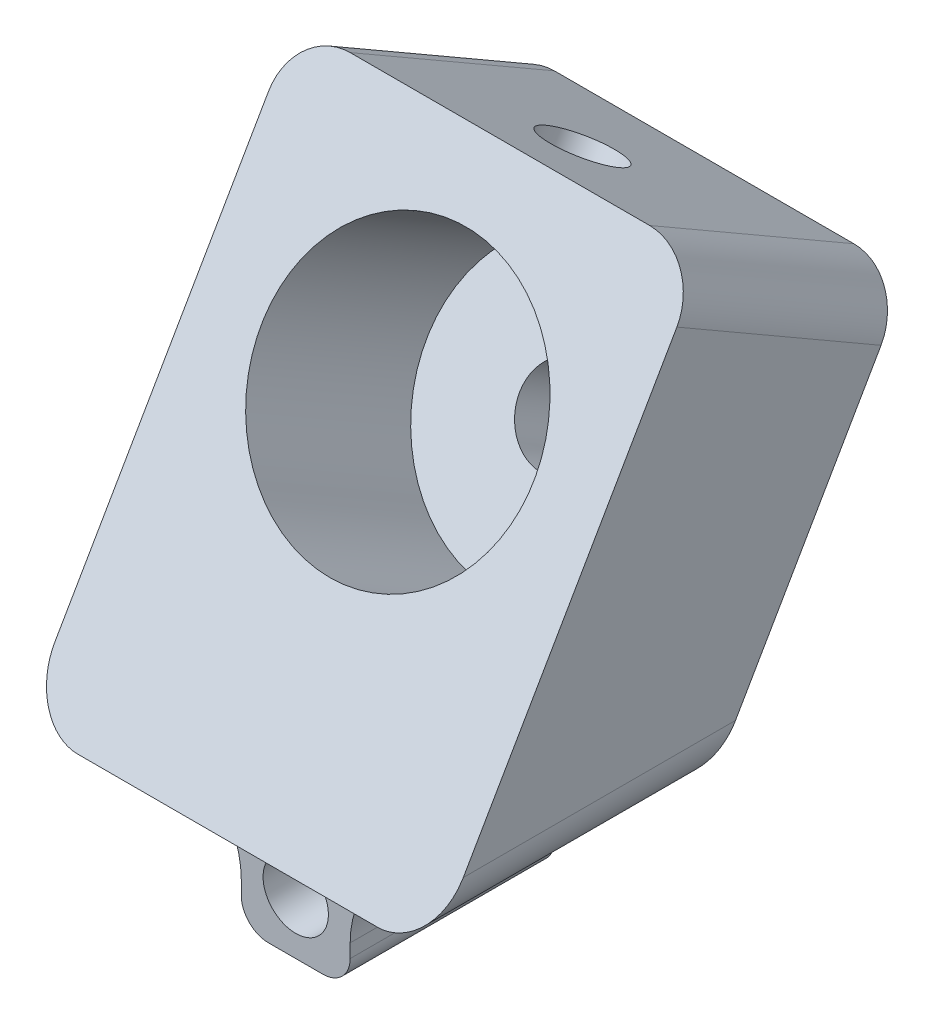
SolidWorks part; units mm, degrees
note: '?' marks a value the reader was unsure of.
ref_plane "Front Plane" through (0, 0, 0) normal (0, 0, 1) x (1, 0, 0)
ref_plane "Top Plane" through (0, 0, 0) normal (0, 1, 0) x (1, 0, 0)
ref_plane "Right Plane" through (0, 0, 0) normal (1, 0, 0) x (0, 0, -1)
sketch "Sketch1" plane through (0, 0, 0) normal (0, 0, 1) x (1, 0, 0)
  line L1 (-2, -2.5) -> (2, -2.5)
  line L2 (-2, -2.5) -> (-2, 2.5)
  line L3 (-2, 2.5) -> (2, 2.5)
  line L4 (2, -2.5) -> (2, 2.5)
  line L5 (-2, -2.5) -> (2, 2.5) construction
  line L6 (-2, 2.5) -> (2, -2.5) construction
  point P0 (0, 0)
  dimension "D1" = 4
  dimension "D2" = 5
extrude "Boss-Extrude1" add sketch "Sketch1" along normal mid plane 7.5
sketch "Sketch2" plane through (0, 0, -3.75) normal (0, 0, -1) x (-1, 0, 0)
  line L1 (-1.55, -2.1) -> (1.55, -2.1)
  line L2 (-1.55, -2.1) -> (-1.55, 1)
  line L3 (-1.55, 1) -> (1.55, 1)
  line L4 (1.55, -2.1) -> (1.55, 1)
  line L5 (-1.55, -2.1) -> (1.55, 1) construction
  line L6 (-1.55, 1) -> (1.55, -2.1) construction
  line L7 (0, 9.625) -> (0, -9.625) construction
  line L10 (-2, 2.5) -> (2, 2.5) construction
  point P0 (0, -0.55)
  dimension "D1" = 3.1
  dimension "D2" = 3.1
  dimension "D3" = 1.5
extrude "Cut-Extrude1" cut sketch "Sketch2" against normal blind 5
sketch "Sketch3" plane through (0, 0, 0) normal (1, 0, 0) x (0, 0, -1)
  line L0 (-6.25, 2.5) -> (3.75, 19.8205)
  line L1 (3.75, 19.8205) -> (11.25, 15.4904)
  line L2 (11.25, 15.4904) -> (3.75, 2.5)
  line L3 (3.75, 2.5) -> (-6.25, 2.5)
  point P3 (0, 0)
  point P7 (0, 0)
  dimension "D1" = 15
  dimension "D2" = 60
  dimension "D3" = 10
extrude "Boss-Extrude2" add sketch "Sketch3" along normal mid plane 15
sketch "Sketch5" plane through (0, -0.9988, -1.73) normal (0, -0.5, -0.866) x (-1, 0, 0)
  line L0 (0, 9.625) -> (0, -9.625) construction
  line L1 (-7.5, 19.0401) -> (7.5, 19.0401) construction
  circle A0 centre (0, 11.5401) radius 1.5875
  point P0 (0, 11.5401)
  dimension "D2" = 3.175
  dimension "D1" = 7.5
hole_wizard "3/8 Clearance Hole1" [suppressed] positions "Sketch6" profile "Sketch7" hole size "3/8" standard "ANSI Inch"
sketch "Sketch6" [suppressed] plane through (0, -0.4575, -0.7925) normal (0, -0.5, -0.866) x (-1, 0, 0)
  point P0 (0, 10.9151)
sketch "Sketch7" [suppressed] plane through (0, 8.9952, -6.25) normal (1, 0, 0) x (0, 0.866, -0.5)
  line L0 (0, 0) -> (0, 14.6142)
  line L1 (0, 14.6142) -> (5.0419, 14.6142)
  line L2 (5.0419, 14.6142) -> (5.0419, 0)
  line L5 (5.0419, 0) -> (0, 0)
  line L11 (0, -6.35) -> (0, 107.95) construction
  dimension "Thru Hole Dia." = 10.0838
  dimension "Thru Hole Depth" = 14.6142
sketch "Sketch8" plane through (0, 0, 3.75) normal (0, 0, 1) x (1, 0, 0)
  line L0 (0, -9.625) -> (0, 9.625) construction
  line L1 (-2, -2.5) -> (2, -2.5) construction
  point P0 (0, -0.5)
  dimension "D1" = 2
hole_wizard "M2 Clearance Hole1" positions "Sketch9" profile "Sketch11" hole size "M2" standard "ANSI Metric" end condition through all
sketch "Sketch9" plane through (0, 0, 3.75) normal (0, 0, 1) x (1, 0, 0)
  point P0 (0, -0.5)
sketch "Sketch11" plane through (0, -0.5, 3.75) normal (1, 0, 0) x (0, -1, 0)
  line L0 (0, 0) -> (0, 15)
  line L1 (0, 15) -> (1.2, 15)
  line L2 (1.2, 15) -> (1.2, 0)
  line L5 (1.2, 0) -> (0, 0)
  line L11 (0, -6.35) -> (0, 107.95) construction
  dimension "Thru Hole Dia." = 2.4
  dimension "Thru Hole Depth" = 15
fillet "Fillet1" radius 3.5 2 edges at (2, 2.5, 0) (-2, 2.5, 0)
fillet "Fillet2" radius 2 4 edges at (-7.5, 17.6554, -7.5) (7.5, 17.6554, -7.5) (7.5, 2.5, 1.25) (-7.5, 2.5, 1.25)
fillet "Fillet3" radius 1 2 edges at (2, -2.5, 0) (-2, -2.5, 0)
ref_axis "Axis1" through (0, 8.9952, -7.5) along (0, 0.5, 0.866)?
sketch "Sketch17" plane through (0, 3.3313, 5.77) normal (0, 0.5, 0.866) x (1, 0, 0)
  circle A0 centre (0, 11.5401) radius 5
  point P0 (0, 11.5401)
  dimension "D1" = 10
extrude "Cut-Extrude2" cut sketch "Sketch17" against normal blind 7
extrude "Cut-Extrude3" cut sketch "Sketch5" against normal blind 5 contours A0
sketch "Sketch18" plane through (0, 16.4892, -9.52) normal (0, 0.866, -0.5) x (1, 0, 0)
  line L0 (0, -9.625) -> (0, 9.625) construction
  line L1 (5.5, -6.6627) -> (-5.5, -6.6627) construction
  circle A0 centre (0, -3.1627) radius 1.35
  point P0 (0, -3.1627)
  dimension "D2" = 2.7
  dimension "D1" = 3.5
fillet "Fillet4" radius 1 1 edges at (0, 2.5, 3.75)
extrude "Cut-Extrude4" cut sketch "Sketch18" against normal blind 5 contours A0
